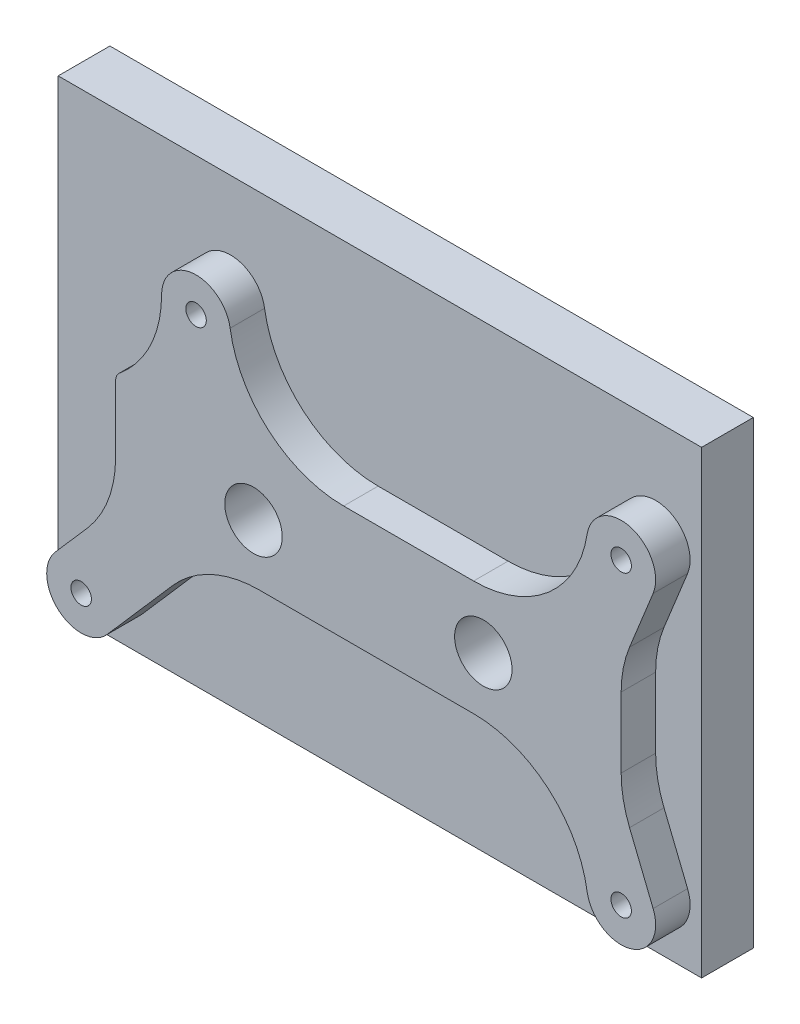
SolidWorks part; units mm, degrees
ref_plane "Front Plane" through (0, 0, 0) normal (0, 0, 1) x (1, 0, 0)
ref_plane "Top Plane" through (0, 0, 0) normal (0, 1, 0) x (1, 0, 0)
ref_plane "Right Plane" through (0, 0, 0) normal (1, 0, 0) x (0, 0, -1)
sketch "Sketch1" plane through (0, 0, 0) normal (0, 0, 1) x (1, 0, 0)
  line L0 (19.05, 39.37) -> (66.04, 39.37) construction
  line L1 (0, 0) -> (71.12, 0)
  line L2 (0, 0) -> (0, 50.8)
  line L3 (0, 50.8) -> (71.12, 50.8)
  line L4 (71.12, 0) -> (71.12, 50.8)
  line L5 (66.04, 39.37) -> (66.04, 6.35) construction
  line L6 (66.04, 6.35) -> (6.35, 6.35) construction
  point P8 (6.35, 6.35)
  point P14 (66.04, 6.35)
  point P15 (66.04, 39.37)
  point P16 (19.05, 39.37)
  dimension "D3" = 59.69
  dimension "D1" = 50.8
  dimension "D2" = 71.12
  dimension "D4" = 33.02
  dimension "D5" = 6.35
  dimension "D6" = 6.35
  dimension "D8" = 12.7
extrude "Boss-Extrude1" add sketch "Sketch1" along normal blind 5.715
sketch "Sketch3" plane through (0, 0, 5.715) normal (0, 0, 1) x (1, 0, 0)
  line L1 (10.16, 29.21) -> (66.04, 29.21)
  line L2 (10.16, 29.21) -> (10.16, 16.51)
  line L3 (10.16, 16.51) -> (66.04, 16.51)
  line L4 (66.04, 29.21) -> (66.04, 16.51)
  circle A0 centre (19.05, 39.37) radius 3.81
  circle A1 centre (66.04, 39.37) radius 3.81
  circle A2 centre (6.35, 6.35) radius 3.81
  circle A3 centre (66.04, 6.35) radius 3.81
  dimension "D1" = 7.62
  dimension "D2" = 3.81
  dimension "D3" = 12.7
  dimension "D4" = 10.16
  dimension "D5" = 55.88
extrude "Boss-Extrude2" add sketch "Sketch3" along normal blind 3.81
hole_wizard "#4-40 Tapped Hole1" positions "Sketch6" profile "Sketch5" tap size "#4-40" standard "ANSI Inch" end condition through all
sketch "Sketch6" plane through (0, 0, 0) normal (0, 0, -1) x (-1, 0, 0)
  point P0 (-66.04, 6.35)
  point P3 (-66.04, 39.37)
  point P6 (-19.05, 39.37)
  point P9 (-6.35, 6.35)
sketch "Sketch5" plane through (66.04, 6.35, 0) normal (1, 0, 0) x (0, 1, 0)
  line L0 (0, 0) -> (0, 9.525)
  line L1 (0, 9.525) -> (1.1303, 9.525)
  line L2 (1.1303, 9.525) -> (1.1303, 0)
  line L5 (1.1303, 0) -> (0, 0)
  line L11 (0, -6.35) -> (0, 107.95) construction
  dimension "Thru Tap Drill Dia." = 2.2606
  dimension "Thru Tap Drill Depth" = 9.525
cosmetic thread "Hole Thread1" parameters "D2"=2.8448
cosmetic thread "Hole Thread2" parameters "D2"=2.8448
cosmetic thread "Hole Thread3" parameters "D2"=2.8448
cosmetic thread "Hole Thread4" parameters "D2"=2.8448
sketch "Sketch7" plane through (0, 0, 5.715) normal (0, 0, 1) x (1, 0, 0)
  line L0 (15.24, 39.37) -> (15.24, 29.21)
  line L1 (66.04, 29.21) -> (10.16, 29.21) construction
  line L2 (15.24, 29.21) -> (22.86, 29.21)
  line L3 (66.04, 29.21) -> (10.16, 29.21) construction
  line L4 (22.86, 29.21) -> (22.86, 39.37)
  line L5 (19.05, 39.37) -> (66.04, 39.37) construction
  line L6 (62.23, 39.37) -> (62.23, 29.21)
  line L7 (3.4795, 8.8552) -> (10.16, 16.51)
  line L8 (9.2205, 3.8448) -> (20.2738, 16.51)
  line L9 (10.16, 16.51) -> (66.04, 16.51) construction
  line L10 (66.04, 29.21) -> (69.572, 37.9413)
  line L11 (62.23, 6.35) -> (62.23, 16.51)
  line L12 (66.04, 6.35) -> (6.35, 6.35) construction
  line L13 (66.04, 16.51) -> (69.572, 7.7787)
  line L14 (10.16, 16.51) -> (20.2738, 16.51)
  line L15 (62.23, 16.51) -> (66.04, 16.51)
  line L16 (62.23, 29.21) -> (66.04, 29.21)
  circle A0 centre (19.05, 39.37) radius 3.81 construction
  circle A1 centre (19.05, 39.37) radius 3.81 construction
  circle A2 centre (66.04, 39.37) radius 3.81 construction
  circle A3 centre (6.35, 6.35) radius 3.81 construction
  circle A4 centre (6.35, 6.35) radius 3.81 construction
  circle A5 centre (66.04, 6.35) radius 3.81 construction
  circle A6 centre (66.04, 6.35) radius 3.81 construction
  circle A7 centre (66.04, 39.37) radius 3.81 construction
  arc A8 (69.572, 7.7787) -> (62.23, 6.35) centre (66.04, 6.35) ccw
  arc A9 (15.24, 39.37) -> (22.86, 39.37) centre (19.05, 39.37) ccw
  arc A10 (62.23, 39.37) -> (69.572, 37.9413) centre (66.04, 39.37) ccw
  arc A11 (9.2205, 3.8448) -> (3.4795, 8.8552) centre (6.35, 6.35) ccw
extrude "Boss-Extrude4" add sketch "Sketch7" along normal up to vertex (3.81 mm away) up to point (10.16, 16.51, 9.525)
fillet "Fillet1" radius 12.7 8 edges at (10.16, 16.51, 7.62) (15.24, 29.21, 7.62) (62.23, 29.21, 7.62) (22.86, 29.21, 7.62) (62.23, 16.51, 7.62) (20.2738, 16.51, 7.62) (66.04, 29.21, 7.62) (66.04, 16.51, 7.62)
fillet "Fillet2" radius 1.27 1 edges at (10.16, 29.21, 7.62)
sketch "Sketch9" plane through (0, 0, 9.525) normal (0, 0, 1) x (1, 0, 0)
  line L0 (38.1, 29.21) -> (38.1, 16.51) construction
  line L1 (49.7266, 29.21) -> (35.3634, 29.21) construction
  line L2 (26.0465, 16.51) -> (49.7266, 16.51) construction
  line L3 (38.1, 22.86) -> (66.04, 22.86) construction
  line L4 (66.04, 18.9814) -> (66.04, 26.7386) construction
  line L5 (38.1, 22.86) -> (10.16, 22.86) construction
  line L6 (10.16, 28.5937) -> (10.16, 21.2725) construction
  line L7 (38.1, 22.86) -> (25.4, 22.86) construction
  line L8 (38.1, 22.86) -> (50.8, 22.86) construction
  line L9 (50.8, 22.86) -> (38.1, 22.86)
  line L10 (38.1, 22.86) -> (25.4, 22.86)
  circle A0 centre (25.4, 22.86) radius 3.175
  circle A1 centre (50.8, 22.86) radius 3.175
  dimension "D2" = 6.35
  dimension "D1" = 12.7
extrude "Cut-Extrude1" cut sketch "Sketch9" along normal blind 2.54 and the other way through all contours A0 | A1
